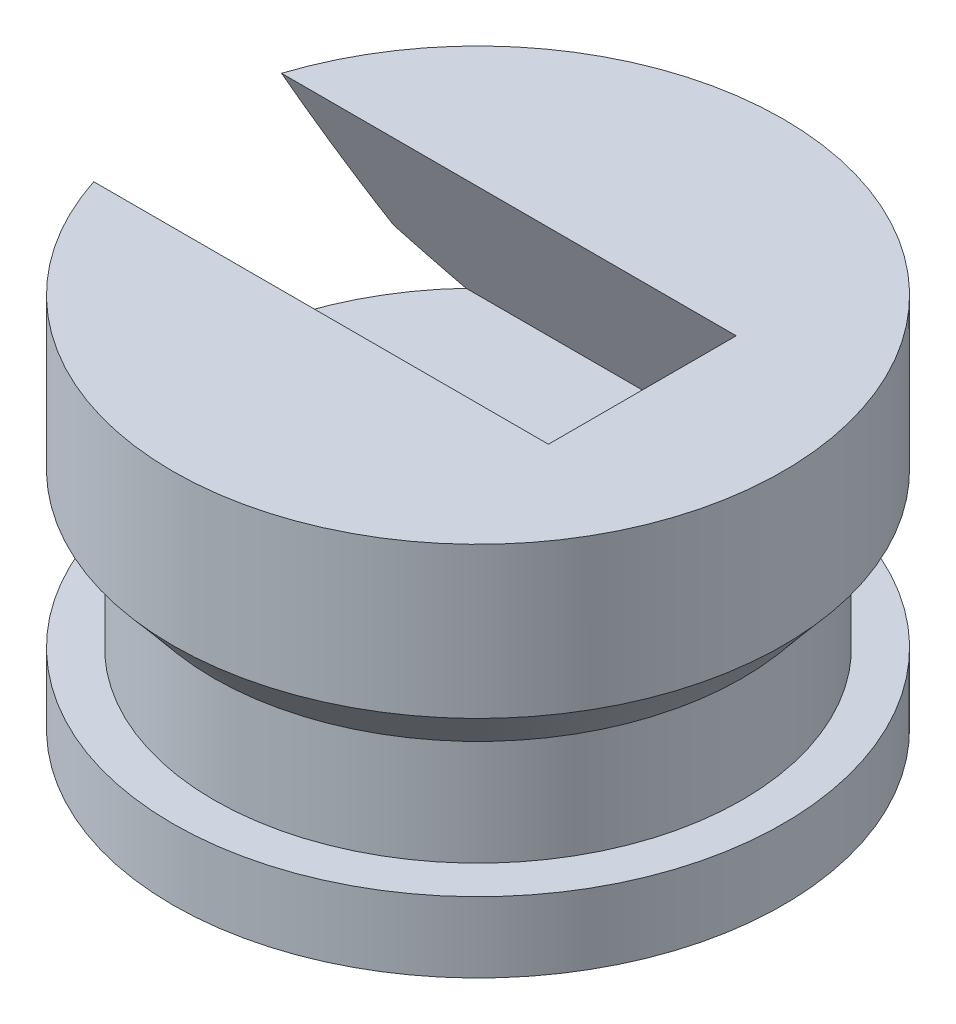
SolidWorks part; units mm, degrees
ref_plane "Front Plane" through (0, 0, 0) normal (0, 0, 1) x (1, 0, 0)
ref_plane "Top Plane" through (0, 0, 0) normal (0, 1, 0) x (1, 0, 0)
ref_plane "Side Plane" through (0, 0, 0) normal (1, 0, 0) x (0, 0, -1)
sketch "Sketch1" plane through (0, 0, 0) normal (0, 1, 0) x (1, 0, 0)
  circle A0 centre (0, 0) radius 13
  dimension "D1" = 26
extrude "Boss-Extrude1" add sketch "Sketch1" along normal blind 3
sketch "Sketch2" plane through (0, 3, 0) normal (0, 1, 0) x (1, 0, 0)
  circle A0 centre (0, 0) radius 11.25
  dimension "D1" = 22.5
extrude "Boss-Extrude2" add sketch "Sketch2" along normal blind 3
sketch "Sketch3" plane through (0, 6, 0) normal (0, 1, 0) x (1, 0, 0)
  circle A0 centre (0, 0) radius 13
  dimension "D1" = 26
extrude "Boss-Extrude4" add sketch "Sketch3" along normal blind 10
sketch "Sketch4" plane through (0, 0, 0) normal (1, 0, 0) x (0, 0, -1)
  line L0 (-11.25, 6) -> (11.25, 6) construction
  line L1 (13, 16) -> (-13, 16) construction
  line L2 (0, 8) -> (-8, 8)
  line L3 (-8, 8) -> (-4, 16)
  line L4 (-4, 16) -> (0, 16)
  line L5 (0, 8) -> (8, 8)
  line L6 (8, 8) -> (4, 16)
  line L7 (4, 16) -> (0, 16)
  dimension "D1" = 16
  dimension "D2" = 8
  dimension "D3" = 4
  dimension "D4" = 8
  dimension "D5" = 2
extrude "Cut-Extrude1" cut sketch "Sketch4" against normal through all and the other way blind 7
chamfer "Chamfer1" distance 3 angle 50 1 edges at (0, 6, 13) first distance on face at (0, 6, 13)
